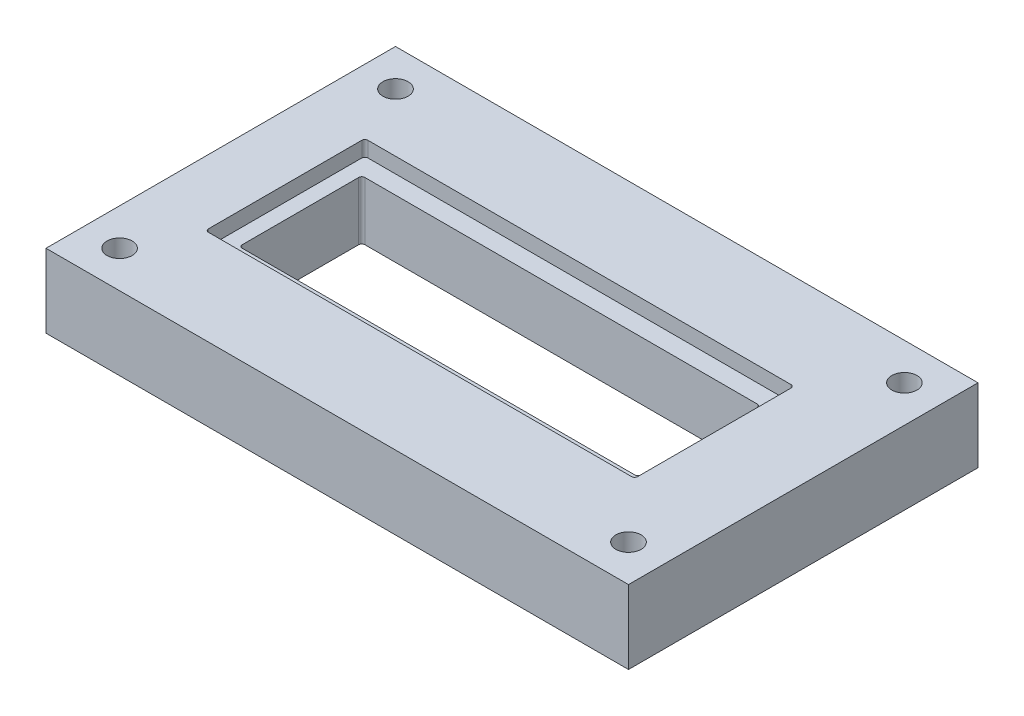
SolidWorks part; units mm, degrees
ref_plane "Front Plane" through (0, 0, 0) normal (0, 0, 1) x (1, 0, 0)
ref_plane "Top Plane" through (0, 0, 0) normal (0, 1, 0) x (1, 0, 0)
ref_plane "Right Plane" through (0, 0, 0) normal (1, 0, 0) x (0, 0, -1)
sketch "Sketch1" plane through (0, 0, 0) normal (0, 1, 0) x (1, 0, 0)
  line L0 (-56.5547, 0) -> (57.1484, 0) construction
  line L1 (47.5, 28.5) -> (-47.5, 28.5)
  line L2 (47.5, 28.5) -> (47.5, -28.5)
  line L3 (47.5, -28.5) -> (-47.5, -28.5)
  line L4 (-47.5, 28.5) -> (-47.5, -28.5)
  line L5 (47.5, 28.5) -> (-47.5, -28.5) construction
  line L6 (47.5, -28.5) -> (-47.5, 28.5) construction
  line L8 (30, -10) -> (-34, -10)
  line L9 (30.5, -9.5) -> (30.5, 9.5)
  line L10 (30, 10) -> (-34, 10)
  line L11 (-34.5, -9.5) -> (-34.5, 9.5)
  line L12 (30.5, -10) -> (-34.5, 10) construction
  line L13 (30.5, 10) -> (-34.5, -10) construction
  line L14 (32.5, 13) -> (-36.5, 13)
  line L15 (33, 12.5) -> (33, -12.5)
  line L16 (32.5, -13) -> (-36.5, -13)
  line L17 (-37, 12.5) -> (-37, -12.5)
  line L18 (33, 13) -> (-37, -13) construction
  line L19 (33, -13) -> (-37, 13) construction
  arc A0 (32.5, -13) -> (33, -12.5) centre (32.5, -12.5) ccw
  arc A1 (32.5, 13) -> (33, 12.5) centre (32.5, 12.5) cw
  arc A2 (-36.5, -13) -> (-37, -12.5) centre (-36.5, -12.5) cw
  arc A3 (-37, 12.5) -> (-36.5, 13) centre (-36.5, 12.5) cw
  arc A4 (-34, -10) -> (-34.5, -9.5) centre (-34, -9.5) cw
  arc A5 (-34, 10) -> (-34.5, 9.5) centre (-34, 9.5) ccw
  arc A6 (30.5, 9.5) -> (30, 10) centre (30, 9.5) ccw
  arc A7 (30, -10) -> (30.5, -9.5) centre (30, -9.5) ccw
  circle A8 centre (-41.5, -22.5) radius 2.058
  circle A9 centre (41.5, -22.5) radius 2.058
  circle A10 centre (-41.5, 22.5) radius 2.058
  circle A11 centre (41.5, 22.5) radius 2.058
  point P0 (0, 0)
  point P8 (-2, 0)
  point P15 (-2, 0)
  point P46 (0, 0)
  point P51 (0, 0)
  dimension "D9" = 0.5
  dimension "D10" = 0.5
  dimension "D11" = 6
  dimension "D13" = 45
  dimension "D1" = 95
  dimension "D2" = 57
  dimension "D3" = 65
  dimension "D4" = 20
  dimension "D5" = 13
  dimension "D6" = 3
  dimension "D7" = 2.5
  dimension "D8" = 26
  dimension "D12" = 83
  dimension "D14" = 6
extrude "Boss-Extrude2" add sketch "Sketch1" along normal blind 12 contours L1 L4 L3 L2 A11 A10 A9 A8 L17 A3 L14 A1 L15 A0 L16 A2 region at (46.3921, 0, 0)
extrude "Boss-Extrude3" add sketch "Sketch1<5>" along normal blind 9.5 contours A3 L17 A2 L16 A0 L15 A1 L14 A7 L8 A4 L11 A5 L10 A6 L9 region at (32.3255, 0, -12.3255)
sketch "Sketch1<5>" plane through (0, 0, 0) normal (0, 1, 0) x (1, 0, 0) same geometry as "Sketch1"
